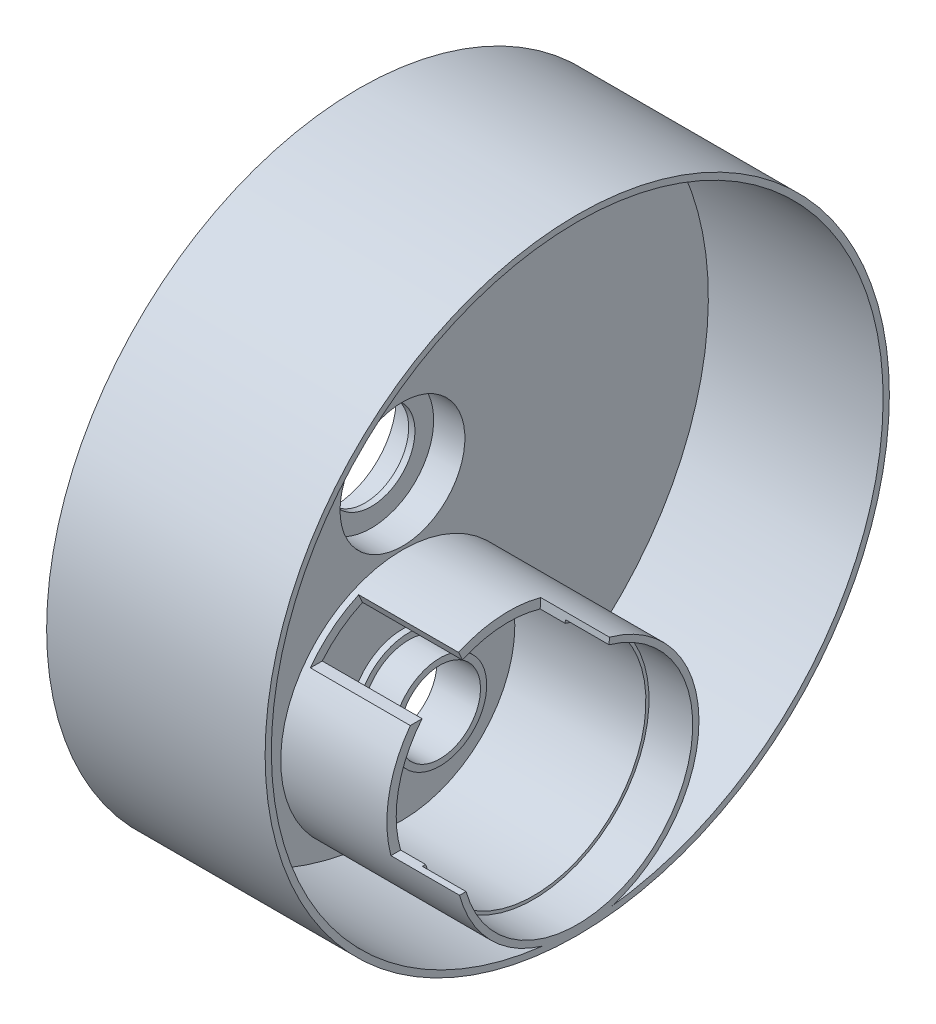
SolidWorks part; units mm, degrees
material "1060 Сплав"
ref_plane "Спереди" through (0, 0, 0) normal (0, 0, 1) x (1, 0, 0)
ref_plane "Сверху" through (0, 0, 0) normal (0, 1, 0) x (1, 0, 0)
ref_plane "Справа" through (0, 0, 0) normal (1, 0, 0) x (0, 0, -1)
sketch "Эскиз1" plane through (0, 0, 0) normal (0, 0, 1) x (1, 0, 0)
  line L0 (0, 0) -> (26039.5549, 0) construction
  line L1 (-27, 7.5) -> (-27, 8.5)
  line L2 (0, 19.5) -> (-29, 19.5)
  line L3 (-29, 19.5) -> (-29, 6.5)
  line L4 (-29, 6.5) -> (-22, 6.5)
  line L5 (-22, 6.5) -> (-22, 7.5)
  line L6 (-22, 7.5) -> (-27, 7.5)
  line L7 (-28, 8.5) -> (-28, 18)
  line L8 (-28, 18) -> (-7, 18)
  line L9 (-7, 18) -> (-7, 18.5)
  line L10 (-7, 18.5) -> (0, 18.5)
  line L11 (0, 18.5) -> (0, 19.5)
  line L12 (-27, 8.5) -> (-28, 8.5)
  dimension "D1" = 18.5
  dimension "D2" = 1
  dimension "D3" = 18
  dimension "D4" = 7
  dimension "D5" = 21
  dimension "D6" = 1
  dimension "D7" = 1
  dimension "D8" = 1
  dimension "D9" = 7.5
  dimension "D10" = 1
  dimension "D11" = 13
  dimension "D12" = 0.5
  dimension "D13" = 5
revolve "Повернуть1" add sketch "Эскиз1" angle 360 about L0
sketch "Эскиз2" plane through (0, 0, 0) normal (1, 0, 0) x (0, 0, -1)
  line L0 (0, 0) -> (0, 50000) construction
  line L1 (5.1563, 18.8059) -> (5, 16.2481)
  line L2 (5, 0) -> (5, 50000) construction
  line L3 (0, 0) -> (0, -5) construction
  line L4 (0, -5) -> (-50000, -5) construction
  line L5 (-18.8481, -5) -> (-16.2481, -5)
  line L6 (-5, 0) -> (-5, 50000) construction
  arc A0 (5, 16.2481) -> (-16.2481, -5) centre (0, 0) ccw
  arc A1 (-18.8481, -5) -> (5.1563, 18.8059) centre (0, 0) cw
  circle A2 centre (0, 0) radius 19.5 construction
  dimension "D3" = 17
  dimension "D4" = 19.5
  dimension "D1" = 5
  dimension "D2" = 5
  dimension "D5" = 2.5626
  dimension "D6" = 0
extrude "Вырез-Вытянуть1" cut sketch "Эскиз2" against normal blind 11 contours A0 L5 A1 L1
sketch "Эскиз3" plane through (0, 0, 0) normal (1, 0, 0) x (0, 0, -1)
  line L3 (-40, 11.5) -> (-12.52, 11.5)
  line L4 (0, 0) -> (-20535.6471, 45588.2353) construction
  line L5 (-6.9821, 15.5) -> (-13.2408, 29.394)
  line L6 (-13.2408, 29.394) -> (-40, 11.5)
  line L7 (0, 15.5) -> (-50000, 15.5) construction
  circle A0 centre (0, 0) radius 15.5 construction
  circle A1 centre (0, 0) radius 11.5 construction
  arc A2 (-6.9821, 15.5) -> (-12.52, 11.5) centre (0, 0) ccw
  dimension "D1" = 31
  dimension "D2" = 23
  dimension "D4" = 34
  dimension "D3" = 15.2386
  dimension "D5" = 32.1908
extrude "Вырез-Вытянуть2" cut sketch "Эскиз3" against normal blind 27
sketch "Эскиз4" plane through (-29, 0, 0) normal (-1, 0, 0) x (0, 0, 1)
  circle A1 centre (0, 30) radius 50
  circle A2 centre (0, 30) radius 10
  circle A3 centre (0, 0) radius 6.5 construction
  circle A4 centre (0, 0) radius 6.5
  dimension "D2" = 100
  dimension "D3" = 20
  dimension "D5" = 13
  dimension "D1" = 30
  dimension "D4" = 30
extrude "Бобышка-Вытянуть1" add sketch "Эскиз4" against normal blind 1
sketch "Эскиз5" plane through (-29, 0, 0) normal (-1, 0, 0) x (0, 0, 1)
  circle A0 centre (0, 30) radius 50
  circle A1 centre (0, 30) radius 49
  dimension "D1" = 100
  dimension "D2" = 98
extrude "Бобышка-Вытянуть2" add sketch "Эскиз5" against normal blind 29 and the other way blind 6
sketch "Эскиз9" plane through (0, 0, 0) normal (0, 0, 1) x (1, 0, 0)
  line L0 (-50.3474, 30) -> (12.875, 30) construction
  line L1 (-39, 40) -> (-34, 40)
  line L2 (-39, 41) -> (-29, 41)
  line L3 (-34, 40) -> (-34, 37)
  line L4 (-34, 37) -> (-33, 37)
  line L5 (-33, 37) -> (-33, 40)
  line L6 (-33, 40) -> (-29, 40)
  line L7 (-29, 40) -> (-29, 41)
  line L8 (-39, 41) -> (-39, 40)
  line L11 (-28, 20) -> (-28, 40) construction
  dimension "D1" = 30
  dimension "D2" = 1
  dimension "D3" = 5
  dimension "D4" = 5
  dimension "D5" = 11
  dimension "D6" = 3
revolve "Повернуть2" add sketch "Эскиз9" angle 360 about L0
sketch "Эскиз12" plane through (-29, 0, 0) normal (-1, 0, 0) x (0, 0, 1)
  line L0 (0, 30) -> (26.4, 30) construction
  circle A0 centre (26.4, 30) radius 5
  dimension "D2" = 10
  dimension "D1" = 26.4
extrude "Вырез-Вытянуть3" cut sketch "Эскиз12" against normal up to next
hole_wizard "Сверление под метчик M2x0.41" positions "Эскиз13" profile "Эскиз14" hole size "M2x0.4" standard "Ansi Metric" end condition through all
sketch "Эскиз13" plane through (-29, 0, 0) normal (-1, 0, 0) x (0, 0, 1)
  line L0 (26.4, 30) -> (26.4, 36.5) construction
  point P0 (26.4, 36.5)
  point P8 (26.4, 41.6612)
  dimension "D1" = 6.5
sketch "Эскиз14" plane through (-29, 36.5, 26.4) normal (0, 1, 0) x (0, 0, 1)
  line L0 (0, 0) -> (0, 29)
  line L1 (0, 29) -> (0.8, 29)
  line L2 (0.8, 29) -> (0.8, 0)
  line L5 (0.8, 0) -> (0, 0)
  line L11 (0, -6.35) -> (0, 107.95) construction
  dimension "Диаметр сквозного отверстия" = 1.6
  dimension "Глубина сквозного отверстия" = 29
pattern_circular "Круговой массив1" count 3 over 360 about axis through (0.001, 30, 26.4) along (-1, 0, 0) of "Сверление под метчик M2x0.41"
